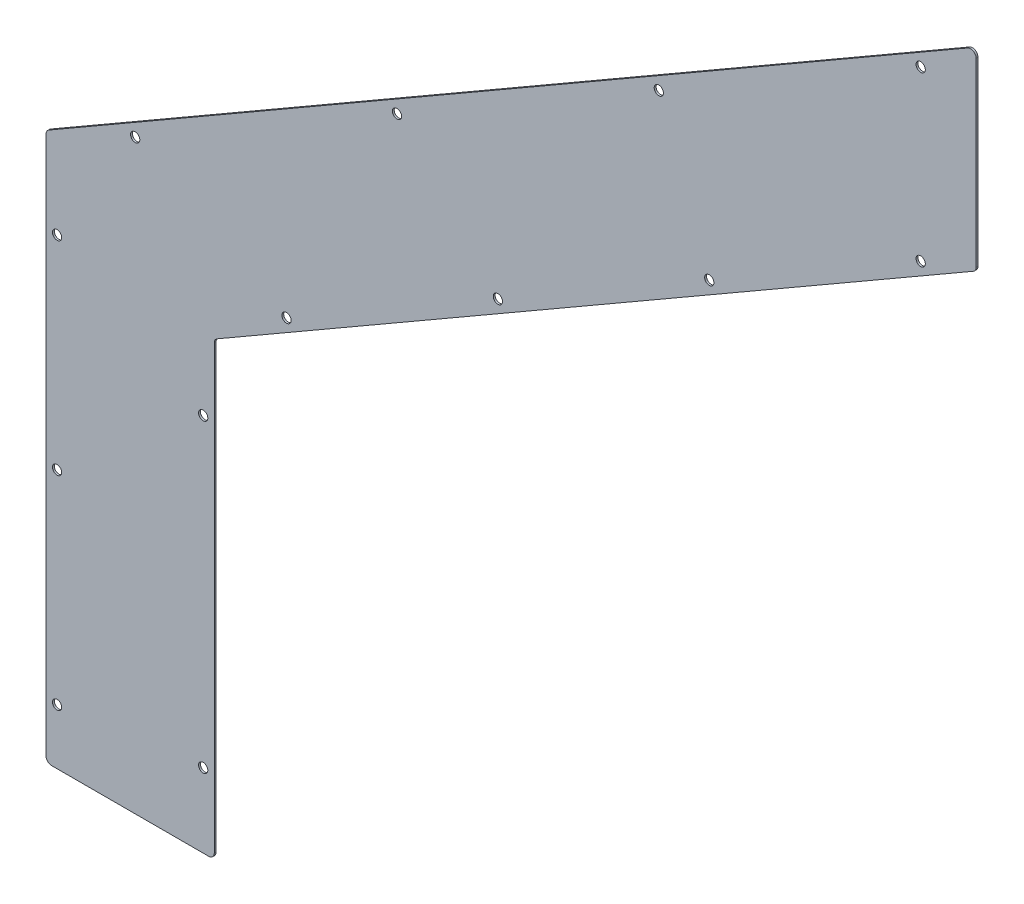
SolidWorks part; units mm, degrees
ref_plane "Front Plane" through (0, 0, 0) normal (0, 0, 1) x (1, 0, 0)
ref_plane "Top Plane" through (0, 0, 0) normal (0, 1, 0) x (1, 0, 0)
ref_plane "Right Plane" through (0, 0, 0) normal (1, 0, 0) x (0, 0, -1)
sketch "Sketch1" plane through (0, 0, 0) normal (0, 0, 1) x (1, 0, 0)
  line L0 (0, 0) -> (0, 243.7367)
  line L1 (0, 243.7367) -> (412, 481.605)
  line L2 (412, 481.605) -> (412, 586.4172)
  line L3 (412, 586.4172) -> (-91, 296.01)
  line L4 (-91, 296.01) -> (-91, 0)
  line L5 (-91, 0) -> (0, 0)
  dimension "D1" = 91
  dimension "D2" = 90.77
  dimension "D3" = 120
  dimension "D4" = 296.01
  dimension "D5" = 503
base flange "Base-Flange1" sketch "Sketch1" thickness 1 reverse thickness direction no parameters "D1"=1
fillet "Fillet1" radius 3 6 edges at (-91, 296.01, -0.5) (-91, 0, -0.5) (0, 0, -0.5) (0, 243.7367, -0.5) (412, 481.605, -0.5) (412, 586.4172, -0.5)
sketch "Sketch2" plane through (0, 0, -1) normal (0, 0, -1) x (-1, 0, 0)
  line L3 (-407.5, 583.8191) -> (89.5, 296.876) construction
  line L4 (-412, 483.3371) -> (-412, 581.221) construction
  line L5 (-1.5, 244.6027) -> (-410.5, 480.739) construction
  line L6 (91, 294.2779) -> (91, 3) construction
  line L7 (0, 3) -> (0, 242.0047) construction
  line L8 (88, 0) -> (3, 0) construction
  circle A0 centre (-382, 562.1685) radius 2.5
  circle A1 centre (-240.4048, 480.4185) radius 2.5
  circle A2 centre (-98.8097, 398.6685) radius 2.5
  circle A3 centre (42.7855, 316.9185) radius 2.5
  circle A4 centre (-382, 471.2127) radius 2.5
  circle A5 centre (-267.6846, 405.2127) radius 2.5
  circle A6 centre (-153.3693, 339.2127) radius 2.5
  circle A7 centre (-39.0539, 273.2127) radius 2.5
  circle A8 centre (85, 30) radius 2.5
  circle A9 centre (6, 40) radius 2.5
  circle A10 centre (85, 140) radius 2.5
  circle A11 centre (85, 250) radius 2.5
  circle A12 centre (6, 205) radius 2.5
  point P4 (-412, 581.221)
  point P5 (91, 294.2779)
  dimension "D1" = 5
  dimension "D2" = 6
  dimension "D3" = 30
  dimension "D4" = 4
  dimension "D5" = 6
  dimension "D7" = 6
  dimension "D8" = 6
  dimension "D9" = 30
  dimension "D12" = 40
  dimension "D6" = 4
  dimension "D10" = 3
  dimension "D11" = 2
extrude "Cut-Extrude1" cut sketch "Sketch2" against normal blind 10 normal cut yes
sketch "Bend-Lines1" [suppressed] plane through (0, 0, 0) normal (0, 1, 0) x (1, 0, 0)
sketch "Bounding-Box1" [suppressed] plane through (0, 0, 0) normal (0, 1, 0) x (1, 0, 0)
sheet metal parameters "Sheet-Metal1" thickness 1 parameters "D1"=1
flat pattern "Flat-Pattern1" [suppressed]
sketch "Bend-Lines2" plane through (0, 0, 0) normal (0, 1, 0) x (1, 0, 0)
sketch3d "Bounding-Box2" [suppressed]
  line L0 (-43.7412, -49.1571, 0) -> (450.6346, 527.7985, 0) construction
  line L1 (-246.7602, 124.8037, 0) -> (247.6157, 701.7593, 0) construction
  line L2 (-43.7412, -49.1571, 0) -> (-246.7602, 124.8037, 0) construction
  line L3 (450.6346, 527.7985, 0) -> (247.6157, 701.7593, 0) construction
sheet metal parameters "Sheet-Metal2" thickness 1 parameters "D1"=1
flat pattern "Flat-Pattern1"
sketch "Bend-Lines2" plane through (0, 0, 0) normal (0, 1, 0) x (1, 0, 0)
sketch3d "Bounding-Box2" [suppressed]
  line L0 (-38.7046, -43.2346, 0) -> (461.6019, 540.055, 0) construction
  line L1 (-236.1709, 126.1386, 0) -> (264.1356, 709.4283, 0) construction
  line L2 (-38.7046, -43.2346, 0) -> (-236.1709, 126.1386, 0) construction
  line L3 (461.6019, 540.055, 0) -> (264.1356, 709.4283, 0) construction
